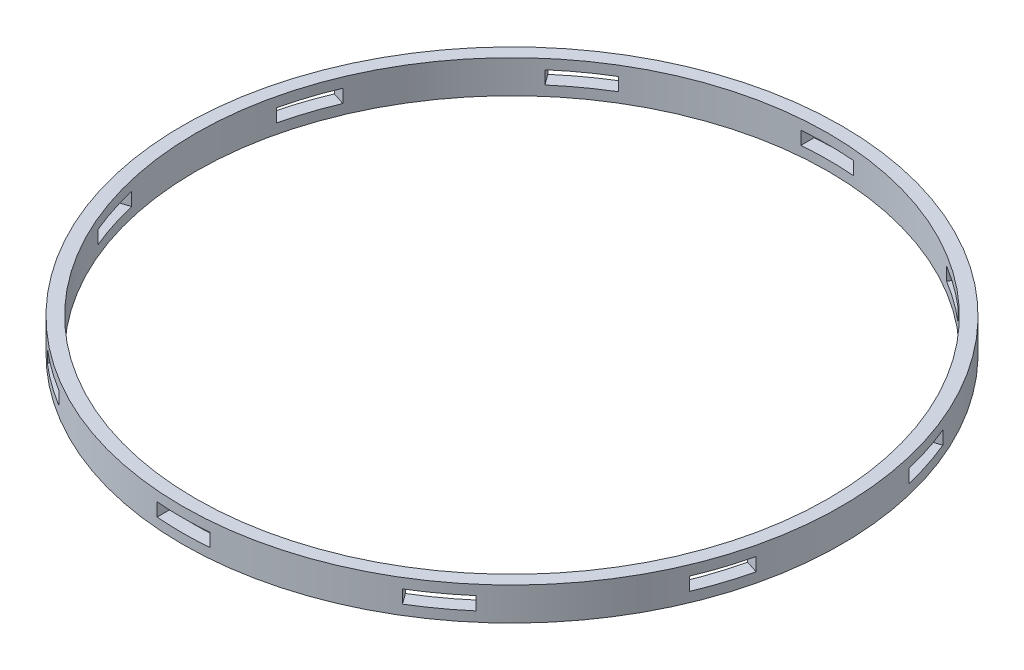
SolidWorks part; units mm, degrees
ref_plane "Front Plane" through (0, 0, 0) normal (0, 0, 1) x (1, 0, 0)
ref_plane "Top Plane" through (0, 0, 0) normal (0, 1, 0) x (1, 0, 0)
ref_plane "Right Plane" through (0, 0, 0) normal (1, 0, 0) x (0, 0, -1)
sketch "Sketch1" plane through (0, 0, 0) normal (0, 1, 0) x (1, 0, 0)
  line L0 (40.8443, 86.8778) -> (42.5461, 90.4977) construction
  circle A0 centre (0, 0) radius 96
  circle A1 centre (0, 0) radius 100
  dimension "D2" = 192
  dimension "D1" = 4
extrude "Boss-Extrude1" add sketch "Sketch1" along normal blind 10
sketch "Sketch2" plane through (0, 0, 0) normal (0, 0, 1) x (1, 0, 0)
  line L0 (-100, 0) -> (100, 0) construction
  line L1 (-8, 7) -> (8, 7)
  line L2 (-8, 7) -> (-8, 3)
  line L3 (-8, 3) -> (8, 3)
  line L4 (8, 7) -> (8, 3)
  line L5 (96, 10) -> (-96, 10) construction
  point P11 (0, 3)
  dimension "D1" = 3
  dimension "D2" = 3
  dimension "D3" = 16
extrude "Cut-Extrude1" cut sketch "Sketch2" against normal through all
ref_axis "Axis1" through (0, 10, 0) along (0, -1, 0)
pattern_circular "CirPattern1" count 10 over 360 about axis through (0, 10, 0) along (0, -1, 0) of "Cut-Extrude1"
